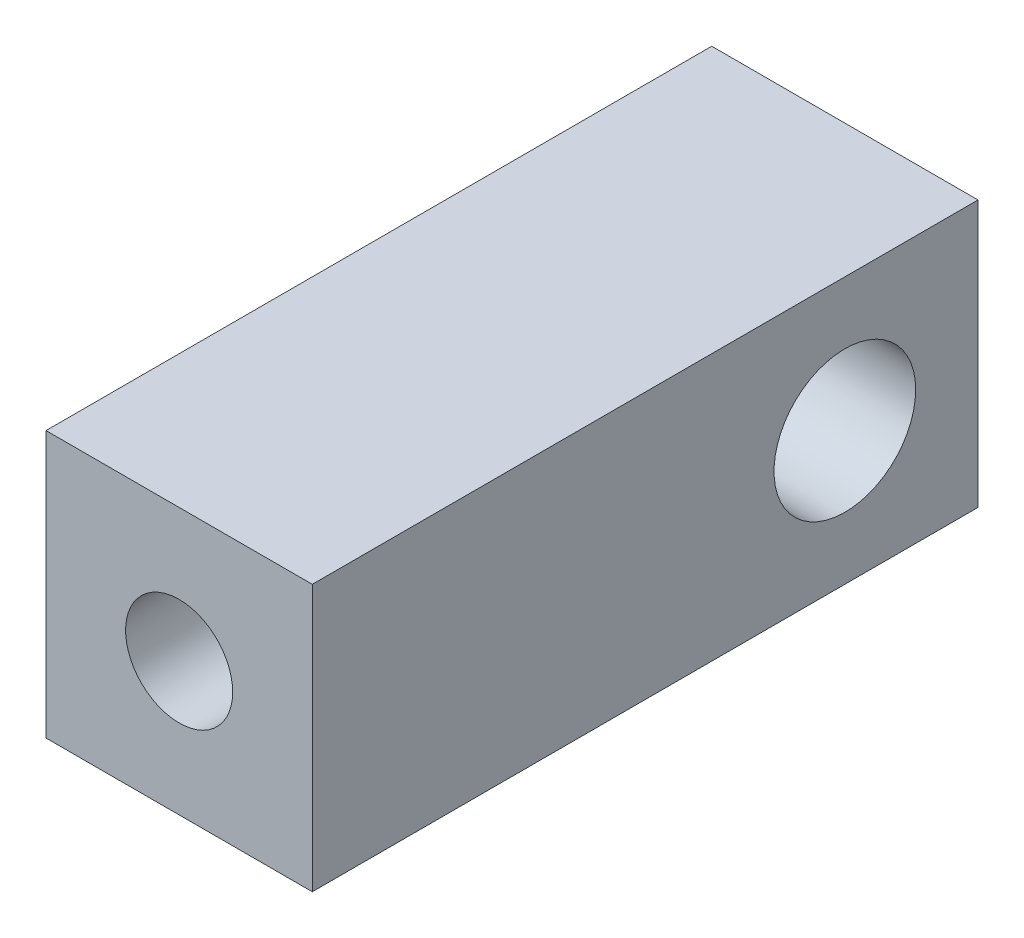
SolidWorks part; units mm, degrees
ref_plane "Front Plane" through (0, 0, 0) normal (0, 0, 1) x (1, 0, 0)
ref_plane "Top Plane" through (0, 0, 0) normal (0, 1, 0) x (1, 0, 0)
ref_plane "Right Plane" through (0, 0, 0) normal (1, 0, 0) x (0, 0, -1)
sketch "Sketch1" plane through (0, 0, 0) normal (1, 0, 0) x (0, 0, -1)
  line L1 (0, 0) -> (31.75, 0)
  line L2 (0, 0) -> (0, 12.7)
  line L3 (0, 12.7) -> (31.75, 12.7)
  line L4 (31.75, 0) -> (31.75, 12.7)
  dimension "D1" = 12.7
  dimension "D2" = 31.75
extrude "Boss-Extrude1" add sketch "Sketch1" along normal blind 12.7
hole_wizard "1/4-20 Tapped Hole1" positions "Sketch2" profile "Sketch3" tap size "1/4-20" standard "ANSI Inch"
sketch "Sketch2" plane through (0, 0, 0) normal (0, 0, 1) x (1, 0, 0)
  line L0 (0, 0) -> (12.7, 12.7) construction
  point P0 (6.35, 6.35)
cosmetic thread "Hole Thread1" parameters "D1"=12.7, "D2"=6.35
sketch "Sketch3" plane through (6.35, 6.35, 0) normal (1, 0, 0) x (0, -1, 0)
  line L0 (0, 0) -> (0, 18.0438)
  line L1 (0, 18.0438) -> (2.5527, 16.51)
  line L2 (2.5527, 16.51) -> (2.5527, 0)
  line L5 (2.5527, 0) -> (0, 0)
  line L10 (0, 18.0438) -> (-2.5527, 16.51) construction
  line L11 (0, -6.35) -> (0, 107.95) construction
  dimension "Tap Drill Dia." = 5.1054
  dimension "Tap Drill Depth" = 16.51
  dimension "Drill Angle" = 118
sketch "Sketch4" plane through (12.7, 0, 0) normal (1, 0, 0) x (0, 0, -1)
  line L0 (31.75, 0) -> (31.75, 12.7) construction
  line L1 (0, 12.7) -> (0, 0) construction
  circle A0 centre (25.4, 6.35) radius 3.3782
  point P4 (0, 0)
  point P7 (0, 6.35)
  dimension "D1" = 6.35
  dimension "D2" = 6.7564
extrude "Cut-Extrude1" cut sketch "Sketch4" against normal through all
